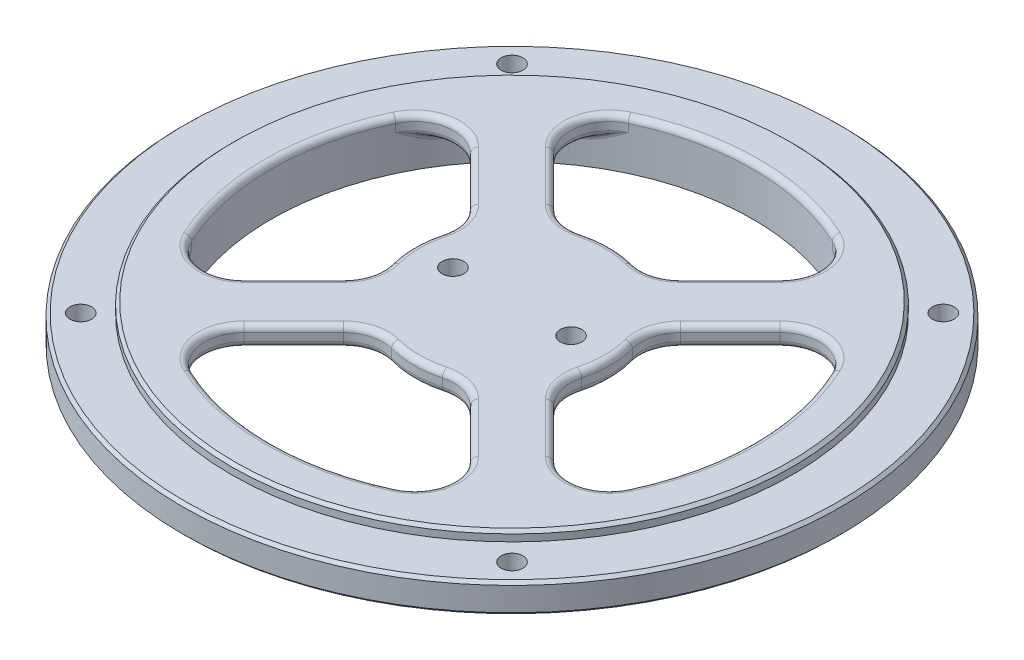
SolidWorks part; units mm, degrees
ref_plane "Front" through (0, 0, 0) normal (0, 0, 1) x (1, 0, 0)
ref_plane "Top" through (0, 0, 0) normal (0, 1, 0) x (1, 0, 0)
ref_plane "Right" through (0, 0, 0) normal (1, 0, 0) x (0, 0, -1)
sketch "Эскиз1" plane through (0, 0, 0) normal (0, 1, 0) x (1, 0, 0)
  circle A0 centre (0, 0) radius 33.5
  dimension "D1" = 67
extrude "Бобышка-Вытянуть1" add sketch "Эскиз1" along normal blind 5
sketch "Эскиз3" plane through (0, 0, 0) normal (0, 1, 0) x (1, 0, 0)
  circle A0 centre (0, 0) radius 26
  circle A1 centre (0, 0) radius 45.0636
  dimension "D1" = 52
extrude "Вырез-Вытянуть1" cut sketch "Эскиз3" along normal blind 1
sketch "Эскиз4" plane through (0, 0, 0) normal (0, 1, 0) x (1, 0, 0)
  circle A0 centre (0, 0) radius 24.5
  dimension "D1" = 49
extrude "Вырез-Вытянуть2" cut sketch "Эскиз4" along normal blind 3
sketch "Эскиз8" plane through (0, 0, 0) normal (0, 1, 0) x (1, 0, 0)
  circle A0 centre (0, 0) radius 28.5
  circle A1 centre (0, 0) radius 44.3897
  dimension "D1" = 57
extrude "Вырез-Вытянуть7" cut sketch "Эскиз8" along normal through all from offset 4
sketch "Эскиз5" plane through (0, 0, 0) normal (0, 1, 0) x (1, 0, 0)
  line L0 (0, 0) -> (21.9203, 21.9203) construction
  circle A0 centre (0, 0) radius 31 construction
  circle A1 centre (21.9203, 21.9203) radius 1.1
  dimension "D1" = 62
extrude "Вырез-Вытянуть4" cut sketch "Эскиз5" along normal through all
pattern_circular "Круговой массив1" count 4 over 360 about axis through (0, 5, 0) along (0, -1, 0) of "Вырез-Вытянуть4" reverse direction yes
sketch "Эскиз6" plane through (0, 0, 0) normal (0, 1, 0) x (1, 0, 0)
  line L0 (0, 0) -> (17.3241, 17.3241)
  line L1 (8.8667, 4.624) -> (19.3151, 15.0724)
  line L2 (4.624, 8.8667) -> (15.0724, 19.3151)
  line L3 (0, 0) -> (17.3241, -17.3241)
  line L4 (-2.1213, 2.1213) -> (15.2028, 19.4454) construction
  line L5 (2.1213, -2.1213) -> (19.4454, 15.2028) construction
  line L6 (4.624, -8.8667) -> (15.0724, -19.3151)
  line L7 (8.8667, -4.624) -> (19.3151, -15.0724)
  line L8 (0, 0) -> (-17.3241, -17.3241)
  line L9 (-8.8667, -4.624) -> (-19.3151, -15.0724)
  line L10 (-4.624, -8.8667) -> (-15.0724, -19.3151)
  line L11 (0, 0) -> (-17.3241, 17.3241)
  line L12 (-4.624, 8.8667) -> (-15.0724, 19.3151)
  line L13 (-8.8667, 4.624) -> (-19.3151, 15.0724)
  circle A0 centre (0, 0) radius 24.5
  circle A1 centre (0, 0) radius 10
  point P31 (0, 0)
  dimension "D1" = 20
  dimension "D2" = 49
  dimension "D3" = 3
  dimension "D4" = 3
  dimension "D5" = 4
extrude "Вырез-Вытянуть5" cut sketch "Эскиз6" along normal through all contours A1 L2 A0 L12 | A1 L13 A0 L9 | A1 L7 A0 L1 | A1 L10 A0 L6 region at (17.3793, 0, 0) region at (0, 0, -17.3793) region at (0, 0, 17.3793) region at (-17.3793, 0, 0)
sketch "Эскиз7" plane through (0, 0, 0) normal (0, 1, 0) x (1, 0, 0)
  circle A0 centre (0, 0) radius 6 construction
  circle A1 centre (6, 0) radius 1.1
  circle A2 centre (-6, 0) radius 1.1
  dimension "D1" = 12
  dimension "D2" = 2.2
  dimension "D3" = 2.2
extrude "Вырез-Вытянуть6" cut sketch "Эскиз7" along normal through all
fillet "Скругление1" radius 4 16 edges at (19.3151, 4, -15.0724) (15.0724, 4, -19.3151) (4.624, 4, -8.8667) (-4.624, 4, -8.8667) (8.8667, 4, -4.624) (8.8667, 4, 4.624) (19.3151, 4, 15.0724) (15.0724, 4, 19.3151) (4.624, 4, 8.8667) (-4.624, 4, 8.8667) (-15.0724, 4, 19.3151) (-19.3151, 4, 15.0724) (-15.0724, 4, -19.3151) (-19.3151, 4, -15.0724) (-8.8667, 4, -4.624) (-8.8667, 4, 4.624)
fillet "Скругление2" radius 0.6 60 edges at (-4.6587, 5, 9.6593) (-8.9775, 5, 13.2201) (-12.6141, 5, 19.2676) (0, 5, 24.5) (12.6141, 5, 19.2676) (8.9775, 5, 13.2201) (4.6587, 5, 9.6593) (4.6587, 5, -9.6593) (8.9775, 5, -13.2201) (12.6141, 5, -19.2676) (0, 5, -24.5) (-12.6141, 5, -19.2676) (-8.9775, 5, -13.2201) (-4.6587, 5, -9.6593) (10, 5, 0) (9.6593, 5, 4.6587) (13.2201, 5, 8.9775) (19.2676, 5, 12.6141) (24.5, 5, 0) (19.2676, 5, -12.6141) (13.2201, 5, -8.9775) (-13.2201, 5, -8.9775) (-19.2676, 5, -12.6141) (-24.5, 5, 0) (-19.2676, 5, 12.6141) (-13.2201, 5, 8.9775) (-9.6593, 5, 4.6587) (-10, 5, 0) (0, 5, 10) (0, 5, -10) (9.6593, 5, -4.6587) (-9.6593, 5, -4.6587) (-12.6141, 3, -19.2676) (-8.9775, 3, -13.2201) (-4.6587, 3, -9.6593) (12.6141, 3, -19.2676) (8.9775, 3, -13.2201) (4.6587, 3, -9.6593) (12.6141, 3, 19.2676) (8.9775, 3, 13.2201) (4.6587, 3, 9.6593) (-12.6141, 3, 19.2676) (-8.9775, 3, 13.2201) (-4.6587, 3, 9.6593) (19.2676, 3, -12.6141) (13.2201, 3, -8.9775) (9.6593, 3, -4.6587) (19.2676, 3, 12.6141) (13.2201, 3, 8.9775) (9.6593, 3, 4.6587) (-19.2676, 3, 12.6141) (-13.2201, 3, 8.9775) (-9.6593, 3, 4.6587) (-10, 3, 0) (-19.2676, 3, -12.6141) (-13.2201, 3, -8.9775) (0, 3, -10) (0, 3, 10) (10, 3, 0) (-9.6593, 3, -4.6587)
fillet "Скругление3" radius 0.6 12 edges at (21.6249, 3.1828, -11.5158) (11.5158, 3.1828, -21.6249) (11.5158, 3.1828, 21.6249) (21.6249, 3.1828, 11.5158) (-21.6249, 3.1828, 11.5158) (-11.5158, 3.1828, 21.6249) (-11.5158, 3.1828, -21.6249) (-21.6249, 3.1828, -11.5158) (17.3241, 3, -17.3241) (17.3241, 3, 17.3241) (-17.3241, 3, 17.3241) (-17.3241, 3, -17.3241)
chamfer "Фаска1" distance 0.3 angle 45 4 edges at (0, 1, 33.5) (0, 0, 26) (0, 5, 28.5) (0, 4, 33.5)
